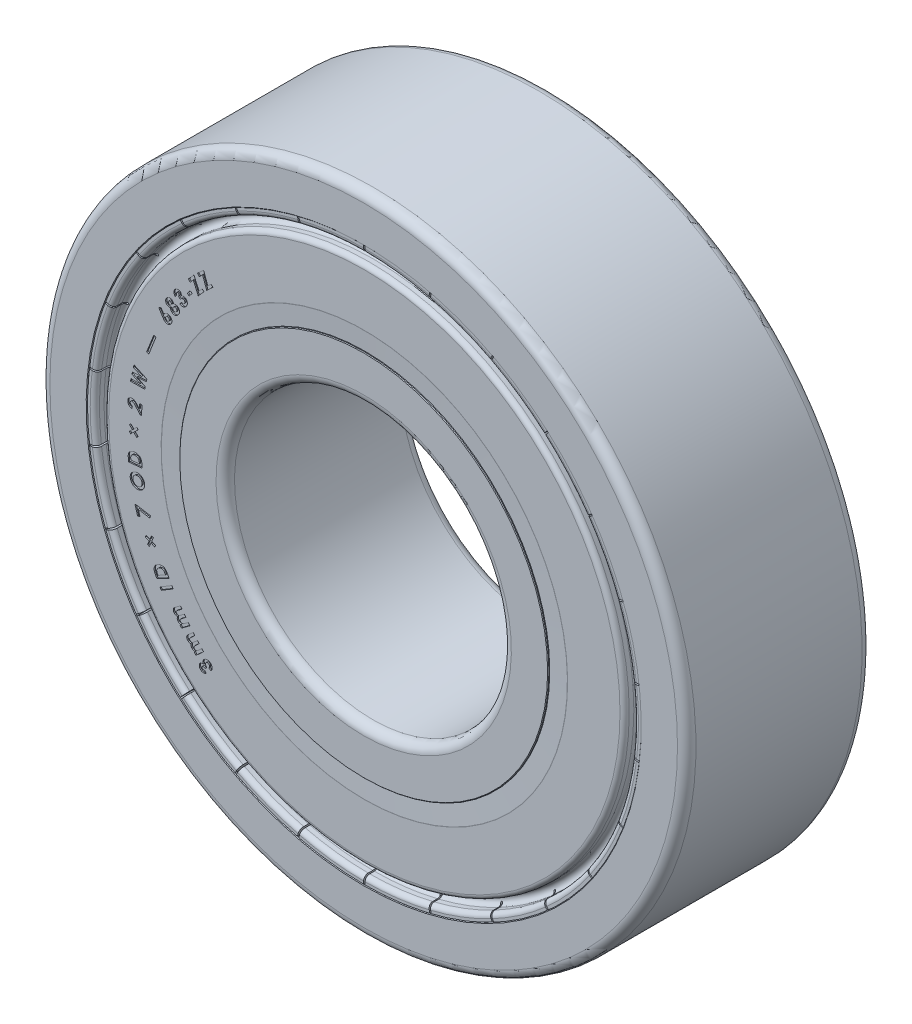
SolidWorks part; units mm, degrees
material "AISI 316 Annealed Stainless Steel Bar (SS)"
ref_plane "Front" through (0, 0, 0) normal (0, 0, 1) x (1, 0, 0)
ref_plane "Top" through (0, 0, 0) normal (0, 1, 0) x (1, 0, 0)
ref_plane "Right" through (0, 0, 0) normal (1, 0, 0) x (0, 0, -1)
sketch "LAYOUT R" plane through (0, 0, 0) normal (1, 0, 0) x (0, 0, -1)
  line L0 (-0.9, 1.5) -> (0.9, 1.5)
  line L1 (1, -3.5) -> (-1, -3.5) construction
  line L2 (1, -3.5) -> (1, 2.5781) construction
  line L3 (0.9, 3.5) -> (-0.9, 3.5)
  line L4 (-1, -3.5) -> (-1, 3.4) construction
  line L6 (2.6982, 0) -> (-2.6982, 0) construction
  line L7 (-0.993, 2) -> (0.993, 2)
  line L8 (-0.993, 3) -> (0.993, 3)
  line L11 (-8.89, 0) -> (8.89, 0) construction
  line L12 (-1, 3.4) -> (-1, 3.007)
  line L13 (1, 3.4) -> (1, 3.007)
  line L16 (-1, 1.993) -> (-1, 1.6)
  line L17 (1, 1.993) -> (1, 1.6)
  line L30 (-0.993, 3) -> (-0.993, 2) construction
  line L31 (0.993, 3) -> (0.993, 2) construction
  line L32 (-0.993, 2.2) -> (0.993, 2.2) construction
  line L33 (-0.993, 2.2) -> (-0.9842, 2)
  line L34 (0.993, 2.2) -> (0.9842, 2)
  line L35 (-0.993, 2.92) -> (0.993, 2.92) construction
  line L38 (-1, 3.007) -> (1, 3.007) construction
  line L39 (-0.993, 3) -> (-0.993, 2.97)
  line L40 (-0.943, 2.92) -> (-0.893, 2.92)
  line L41 (-0.993, 2.2022) -> (-0.993, 2.77)
  line L42 (-0.943, 2.82) -> (-0.893, 2.82)
  line L43 (0.993, 2.2022) -> (0.993, 2.77)
  line L44 (0.943, 2.82) -> (0.893, 2.82)
  line L45 (0.943, 2.92) -> (0.893, 2.92)
  line L46 (-0.993, 2.82) -> (0.993, 2.82) construction
  line L50 (-1.3199, 2.8) -> (1.3199, 2.8) construction
  line L53 (0.993, 2) -> (1, 1.993)
  line L54 (-0.993, 2) -> (-1, 1.993)
  line L56 (-1, 1.993) -> (1, 1.993) construction
  line L57 (1, 3.007) -> (0.993, 3) construction
  line L58 (1, 3.007) -> (0.993, 3)
  line L60 (-1, 3.007) -> (-0.993, 3) construction
  line L61 (-1, 3.007) -> (-0.993, 3)
  line L64 (-0.893, 2.82) -> (-0.893, 2.92) construction
  line L65 (0.893, 2.82) -> (0.893, 2.92) construction
  line L66 (0.993, 3) -> (0.993, 2.97)
  arc A2 (-0.943, 2.82) -> (-0.993, 2.77) centre (-0.943, 2.77) ccw
  arc A3 (0.993, 2.77) -> (0.943, 2.82) centre (0.943, 2.77) ccw
  arc A4 (0.993, 2.2) -> (0.993, 2.2022) centre (0.943, 2.2022) ccw
  arc A5 (-0.993, 2.2022) -> (-0.993, 2.2) centre (-0.943, 2.2022) ccw
  arc A6 (-0.893, 2.82) -> (-0.893, 2.92) centre (-0.893, 2.87) ccw
  arc A7 (0.893, 2.92) -> (0.893, 2.82) centre (0.893, 2.87) ccw
  arc A8 (-0.9, 3.5) -> (-1, 3.4) centre (-0.9, 3.4) ccw
  arc A9 (-1, 1.6) -> (-0.9, 1.5) centre (-0.9, 1.6) ccw
  arc A10 (0.9, 1.5) -> (1, 1.6) centre (0.9, 1.6) ccw
  arc A11 (-0.993, 2.97) -> (-0.943, 2.92) centre (-0.943, 2.97) ccw
  arc A12 (0.943, 2.92) -> (0.993, 2.97) centre (0.943, 2.97) ccw
  arc A13 (1, 3.4) -> (0.9, 3.5) centre (0.9, 3.4) ccw
  point P0 (0, 0)
  point P7 (-0.9, 3.5)
  point P8 (-0.943, 2.92)
  point P15 (0, 0)
  point P29 (-0.993, 2.97)
  point P38 (-0.993, 2.2)
  point P54 (-0.993, 2.77)
  point P55 (-0.943, 2.82)
  point P56 (-0.993, 2.77)
  point P58 (-0.993, 2.2022)
  point P59 (-0.993, 2.2)
  point P60 (0.943, 2.82)
  point P62 (0.993, 2.77)
  point P63 (0.993, 2.2022)
  point P64 (0.993, 2.2)
  point P71 (-1, 3.4)
  point P72 (-1, 1.6)
  point P73 (-0.9, 1.5)
  point P74 (0.9, 1.5)
  point P75 (1, 1.6)
  point P80 (0.9, 3.5)
  point P81 (0.943, 2.92)
  point P88 (0.993, 2.97)
  point P91 (1, 3.4)
  dimension "D21" = 0.1
  dimension "D33" = 0.1
  dimension "D3" = 1.5
  dimension "D4" = 2
  dimension "D5" = 3
  dimension "D24" = 2
  dimension "D6" = 1.993
  dimension "D7" = 1.993
  dimension "D11" = 0.2
  dimension "D12" = 2.5
  dimension "D13" = 2.5
  dimension "D14" = 0.08
  dimension "D17" = 0.007
  dimension "D18" = 0.1
  dimension "D19" = 0.1
  dimension "D20" = 0.1
  dimension "D15" = 0.2
  dimension "D23" = 45
  dimension "D25" = 45
  dimension "D27" = 0.007
  dimension "D28" = 3.5
  dimension "D29" = 2
  dimension "D30" = 7
  dimension "D8" = 1
  dimension "D31" = 45
  dimension "D32" = 45
sketch "Sketch R, INNER BODY" plane through (0, 0, 0) normal (1, 0, 0) x (0, 0, -1)
  line L1 (-0.993, 2) -> (-1, 1.993) construction
  line L3 (-1, 1.993) -> (-1, 1.6) construction
  line L12 (-8.89, 0) -> (8.89, 0) construction
  line L13 (-8.89, 0) -> (8.89, 0) construction
  line L14 (-0.9, 1.5) -> (0.9, 1.5) construction
  line L15 (1, 1.993) -> (1, 1.6) construction
  line L16 (0.993, 2) -> (1, 1.993) construction
  line L17 (-0.993, 2) -> (0.993, 2) construction
  line L18 (-0.993, 2) -> (-1, 1.993)
  line L19 (-1, 1.993) -> (-1, 1.6)
  line L20 (-0.9, 1.5) -> (0.9, 1.5)
  line L21 (1, 1.993) -> (1, 1.6)
  line L22 (0.993, 2) -> (1, 1.993)
  line L23 (-0.993, 2) -> (0.993, 2)
  arc A0 (-1, 1.6) -> (-0.9, 1.5) centre (-0.9, 1.6) ccw construction
  arc A1 (0.9, 1.5) -> (1, 1.6) centre (0.9, 1.6) ccw construction
  arc A2 (-1, 1.6) -> (-0.9, 1.5) centre (-0.9, 1.6) ccw
  arc A3 (0.9, 1.5) -> (1, 1.6) centre (0.9, 1.6) ccw
sketch "Sketch R, OUTER BODY" plane through (0, 0, 0) normal (1, 0, 0) x (0, 0, -1)
  line L8 (-8.89, 0) -> (8.89, 0) construction
  line L9 (-8.89, 0) -> (8.89, 0) construction
  line L31 (-1, 3.4) -> (-1, 3.007) construction
  line L84 (-1, 3.007) -> (-0.993, 3) construction
  line L85 (-0.993, 3) -> (0.993, 3) construction
  line L86 (1, 3.007) -> (0.993, 3) construction
  line L87 (1, 3.4) -> (1, 3.007) construction
  line L88 (0.9, 3.5) -> (-0.9, 3.5) construction
  line L89 (-1, 3.4) -> (-1, 3.007)
  line L90 (-1, 3.007) -> (-0.993, 3)
  line L91 (-0.993, 3) -> (0.993, 3)
  line L92 (1, 3.007) -> (0.993, 3)
  line L93 (1, 3.4) -> (1, 3.007)
  line L94 (0.9, 3.5) -> (-0.9, 3.5)
  arc A6 (1, 3.4) -> (0.9, 3.5) centre (0.9, 3.4) ccw construction
  arc A7 (-0.9, 3.5) -> (-1, 3.4) centre (-0.9, 3.4) ccw construction
  arc A8 (1, 3.4) -> (0.9, 3.5) centre (0.9, 3.4) ccw
  arc A9 (-0.9, 3.5) -> (-1, 3.4) centre (-0.9, 3.4) ccw
sketch "Sketch R, SHIELD FACES" plane through (0, 0, 0) normal (1, 0, 0) x (0, 0, -1)
  line L0 (-8.89, 0) -> (8.89, 0) construction
  line L1 (-8.89, 0) -> (8.89, 0) construction
  line L29 (-0.993, 3) -> (-0.993, 2.97) construction
  line L32 (-0.943, 2.92) -> (-0.893, 2.92) construction
  line L34 (-0.943, 2.82) -> (-0.893, 2.82) construction
  line L36 (-0.993, 2.2022) -> (-0.993, 2.77) construction
  line L38 (-0.993, 2.2) -> (-0.9842, 2) construction
  line L39 (-0.993, 2) -> (0.993, 2) construction
  line L40 (0.993, 2.2) -> (0.9842, 2) construction
  line L43 (0.993, 2.2022) -> (0.993, 2.77) construction
  line L79 (0.943, 2.82) -> (0.893, 2.82) construction
  line L80 (0.943, 2.92) -> (0.893, 2.92) construction
  line L81 (0.993, 3) -> (0.993, 2.97) construction
  line L82 (-0.993, 3) -> (0.993, 3) construction
  line L83 (-0.993, 3) -> (-0.993, 2.97)
  line L84 (-0.943, 2.92) -> (-0.893, 2.92)
  line L85 (-0.943, 2.82) -> (-0.893, 2.82)
  line L86 (-0.993, 2.2022) -> (-0.993, 2.77)
  line L87 (-0.993, 2.2) -> (-0.9842, 2)
  line L88 (-0.9842, 2) -> (0.9842, 2)
  line L89 (0.993, 2.2) -> (0.9842, 2)
  line L90 (0.993, 2.2022) -> (0.993, 2.77)
  line L91 (0.943, 2.82) -> (0.893, 2.82)
  line L92 (0.943, 2.92) -> (0.893, 2.92)
  line L93 (0.993, 3) -> (0.993, 2.97)
  line L94 (-0.993, 3) -> (0.993, 3)
  arc A28 (-0.993, 2.97) -> (-0.943, 2.92) centre (-0.943, 2.97) ccw construction
  arc A29 (-0.893, 2.82) -> (-0.893, 2.92) centre (-0.893, 2.87) ccw construction
  arc A30 (-0.943, 2.82) -> (-0.993, 2.77) centre (-0.943, 2.77) ccw construction
  arc A31 (0.993, 2.77) -> (0.943, 2.82) centre (0.943, 2.77) ccw construction
  arc A32 (0.893, 2.92) -> (0.893, 2.82) centre (0.893, 2.87) ccw construction
  arc A33 (0.943, 2.92) -> (0.993, 2.97) centre (0.943, 2.97) ccw construction
  arc A34 (-0.993, 2.97) -> (-0.943, 2.92) centre (-0.943, 2.97) ccw
  arc A35 (-0.893, 2.82) -> (-0.893, 2.92) centre (-0.893, 2.87) ccw
  arc A36 (-0.943, 2.82) -> (-0.993, 2.77) centre (-0.943, 2.77) ccw
  arc A37 (0.993, 2.77) -> (0.943, 2.82) centre (0.943, 2.77) ccw
  arc A38 (0.893, 2.92) -> (0.893, 2.82) centre (0.893, 2.87) ccw
  arc A39 (0.943, 2.92) -> (0.993, 2.97) centre (0.943, 2.97) ccw
  arc A40 (-0.993, 2.2022) -> (-0.993, 2.2) centre (-0.943, 2.2022) ccw construction
  arc A41 (-0.993, 2.2022) -> (-0.993, 2.2) centre (-0.943, 2.2022) ccw
  arc A42 (0.993, 2.2) -> (0.993, 2.2022) centre (0.943, 2.2022) ccw construction
  arc A43 (0.993, 2.2) -> (0.993, 2.2022) centre (0.943, 2.2022) ccw
revolve "Revolve INNER BODY" add sketch "Sketch R, INNER BODY" angle 360 about L13
revolve "Revolve OUTER BODY" add sketch "Sketch R, OUTER BODY" angle 360 about L9
revolve "Revolve SHIELDS" add sketch "Sketch R, SHIELD FACES" angle 360 about L1
sketch "Sketch TEXT RADIUS 1 — MANUALLY ASSIGN TEXT AND FONT SIZE (FROM EQUATIONS)" plane through (0, 0, 0.993) normal (0, 0, 1) x (1, 0, 0)
  circle A0 centre (0, 0) radius 2.425 construction
  text T0 "<b>3mm ID × 7 OD × 2 W  —  683-ZZ</b>" font "Century Gothic" height 0.15
  dimension "D1" = 4.85
extrude "Cut-Extrude LABEL 1" cut sketch "Sketch TEXT RADIUS 1 — MANUALLY ASSIGN TEXT AND FONT SIZE (FROM EQUATIONS)" against normal blind 0.0127
sketch "Sketch TEXT RADIUS 2 — MANUALLY ASSIGN TEXT AND FONT SIZE (FROM EQUATIONS)" plane through (0, 0, -0.993) normal (0, 0, -1) x (-1, 0, 0)
  circle A0 centre (0, 0) radius 2.425 construction
  text T0 "<b>3mm ID × 7 OD × 2 W  —  683-ZZ</b>" font "Century Gothic" height 0.15
  dimension "D1" = 4.85
extrude "Cut-Extrude LABEL 2" cut sketch "Sketch TEXT RADIUS 2 — MANUALLY ASSIGN TEXT AND FONT SIZE (FROM EQUATIONS)" against normal blind 0.0127
sketch "LAYOUT F, SLIT SEED" plane through (0, 0, 0) normal (0, 0, 1) x (1, 0, 0)
  line L0 (0, 0) -> (0, 12.7) construction
  line L3 (0.008, 3) -> (0.008, 2.9089)
  line L4 (-0.008, 3) -> (-0.008, 2.9089)
  circle A4 centre (0, 0) radius 2.9
  circle A5 centre (0, 0) radius 3
  circle A6 centre (0, 2.9) radius 0.012
  point P13 (-0.008, 3)
  point P15 (0.008, 3)
  dimension "D1" = 6
  dimension "D2" = 5.8
  dimension "D3" = 0.024
  dimension "D4" = 0.008
  dimension "D5" = 0.008
sketch "Sketch F, SLIT SEED" plane through (0, 0, 0.993) normal (0, 0, 1) x (1, 0, 0)
  line L1 (0.008, 3) -> (0.008, 2.9089) construction
  line L8 (-0.008, 3) -> (-0.008, 2.9089) construction
  line L9 (0.008, 3) -> (0.008, 2.9089)
  line L10 (-0.008, 3) -> (-0.008, 2.9089)
  circle A1 centre (0, 2.9) radius 0.012 construction
  circle A8 centre (0, 0) radius 3 construction
  arc A9 (-0.008, 2.9089) -> (0.008, 2.9089) centre (0, 2.9) ccw
  arc A10 (0.008, 3) -> (-0.008, 3) centre (0, 0) ccw
extrude "Cut-Extrude SLIT SEED F" cut sketch "Sketch F, SLIT SEED" along normal blind 0.635 from surface starting at face at (2.0812, 1.388, -0.993)
extrude "Cut-Extrude SLIT SEED B" cut sketch "Sketch F, SLIT SEED<2>" against normal blind 0.635
sketch "Sketch F, SLIT SEED<2>" plane through (0, 0, 0.993) normal (0, 0, 1) x (1, 0, 0) same geometry as "Sketch F, SLIT SEED"
pattern_circular "CirPattern1" count 26 over 360 of "Cut-Extrude SLIT SEED F"
pattern_circular "CirPattern2" count 26 over 360 of "Cut-Extrude SLIT SEED B" reverse direction yes
equation "\"_i__BORE\" = 3"
equation "\"_i__OUTSIDE_DIAMETER\" = 7"
equation "\"_i__WIDTH\"= 2"
equation "\"_user_applied_FONT_SIZE\"= int ( \"BODY_SPAN__SHIELD__OF_RADIUS\" * \"g_param__FONT_SIZE_RATIO\" * 100 ) / 100'MANUALLY ASSIGN TO FONT"
equation "\"BODY__HALF_WIDTH\"= \"_i__WIDTH\" / 2"
equation "\"BODY_SPAN___OF_DIAMETER\"= \"_i__OUTSIDE_DIAMETER\" - \"_i__BORE\""
equation "\"BODY_SPAN___OF_RADIUS\"= \"BODY_SPAN___OF_DIAMETER\" / 2"
equation "\"BODY_SPAN__BORE_AND_OD__OF RADIUS\"= ( \"BODY_SPAN___OF_RADIUS\" - \"BODY_SPAN__SHIELD__OF_RADIUS\" ) / 2"
equation "\"BODY_SPAN__SHIELD__OF_RADIUS\"= \"BODY_SPAN___OF_RADIUS\" * \"g_param__SHIELD_PANEL_SPAN__RATIO_OF_BODY_RADIAN\""
equation "\"BORE__RADIUS\"= \"_i__BORE\" / 2"
equation "\"CORNER_RADII\"= \"_i__WIDTH\" * \"g_param__CORNER_RADII__RATIO_TO_WIDTH\""
equation "\"OUTSIDE_RADIUS\"= \"_i__OUTSIDE_DIAMETER\" / 2"
equation "\"RING_INNER__OUTSIDE_RADIUS\"= \"BORE__RADIUS\" + \"BODY_SPAN__BORE_AND_OD__OF RADIUS\""
equation "\"RING_OUTER__INSIDE_DIAMETER\"= \"RING_OUTER__INSIDE_RADIUS\" * 2"
equation "\"RING_OUTER__INSIDE_RADIUS\"= ( \"_i__OUTSIDE_DIAMETER\" / 2 ) - \"BODY_SPAN__BORE_AND_OD__OF RADIUS\""
equation "\"SHIELD__BOTTOM_AND_TOP_REGIONS_SPAN\"= \"BODY_SPAN__SHIELD__OF_RADIUS\" * \"g_param__SHIELD__TOP_AND_BOTTOM_REGIONS_RATIO\""
equation "\"SHIELD__COMPRESSION_FILLET_DIAMETER\"= \"BODY_SPAN__SHIELD__OF_RADIUS\" * \"g_param__SHIELD_COMPRESSION_FILLET_DIAMETER_RATIO\""
equation "\"SHIELD__COMPRESSION_FILLET_RADIUS\"= \"SHIELD__COMPRESSION_FILLET_DIAMETER\" / 2"
equation "\"SHIELD__FACE_FILLET_DIAMETER\"= \"BODY_SPAN__SHIELD__OF_RADIUS\" * \"g_param__SHIELD_FACE_FILLET_RATIO\""
equation "\"SHIELD__FACE_INSET\"= \"SIDE_FACE_CHAMFERS\""
equation "\"SHIELD__FACE_TO_OPPOSING_BRG_BODY_FACE\"= \"_i__WIDTH\" - \"SHIELD__FACE_INSET\""
equation "\"SHIELD__HALF_SLIT_WIDTH\"= \"SHIELD__SLIT_WIDTH\" / 2"
equation "\"SHIELD__HALF_WALL\"= \"SHIELD__WALL\" / 2"
equation "\"SHIELD__SLIT_WIDTH\"= \"SHIELD__WALL\" / 5"
equation "\"SHIELD__WALL\"= \"BODY_SPAN__SHIELD__OF_RADIUS\" * \"g_param__SHIELD_WALL_TO_SPAN_RATIO\""
equation "\"SHIELD_SLIT__INSIDE_TERMINUS__DIAMETER\"= \"RING_OUTER__INSIDE_DIAMETER\" - \"SHIELD__BOTTOM_AND_TOP_REGIONS_SPAN\""
equation "\"SHIELD_SLIT__KEYHOLE_DIAMETER\"= \"SHIELD__SLIT_WIDTH\" * 1.5"
equation "\"SIDE_FACE_CHAMFERS\"= \"_i__OUTSIDE_DIAMETER\" * \"g_param__SIDE_CHAMFERS__RATIO_TO_OD\""
equation "\"TEXT_RADIUS\"= \"_i__BORE\" + ( \"BODY_SPAN___OF_DIAMETER\" / 2 ) - \"_user_applied_FONT_SIZE\""
equation "\"WIDTH__HALF\"= \"_i__WIDTH\" / 2"
equation "\"D1@CirPattern1\" = \"g_param__SHIELD__NUMBER_OF_SLITS\""
equation "\"D1@CirPattern2\" = \"g_param__SHIELD__NUMBER_OF_SLITS\""
equation "\"D1@LAYOUT F, SLIT SEED\"=\"RING_OUTER__INSIDE_DIAMETER\""
equation "\"D1@Sketch TEXT RADIUS 1 — MANUALLY ASSIGN TEXT AND FONT SIZE (FROM EQUATIONS)\" = \"TEXT_RADIUS\""
equation "\"D1@Sketch TEXT RADIUS 2 — MANUALLY ASSIGN TEXT AND FONT SIZE (FROM EQUATIONS)\" = \"TEXT_RADIUS\""
equation "\"D11@LAYOUT R\"=\"SHIELD__BOTTOM_AND_TOP_REGIONS_SPAN\""
equation "\"D12@LAYOUT R\" = \"g_param__SHIELD__INSIDE_BEVEL_ANGLE__DEGREES\""
equation "\"D13@LAYOUT R\"= \"g_param__SHIELD__INSIDE_BEVEL_ANGLE__DEGREES\""
equation "\"D14@LAYOUT R\"=\"SHIELD__WALL\""
equation "\"D15@LAYOUT R\"=\"SHIELD__BOTTOM_AND_TOP_REGIONS_SPAN\""
equation "\"D17@LAYOUT R\"=\"SIDE_FACE_CHAMFERS\""
equation "\"D18@LAYOUT R\"=\"SHIELD__COMPRESSION_FILLET_DIAMETER\""
equation "\"D19@LAYOUT R\"=\"SHIELD__COMPRESSION_FILLET_DIAMETER\""
equation "\"D2@LAYOUT F, SLIT SEED\"=\"SHIELD_SLIT__INSIDE_TERMINUS__DIAMETER\""
equation "\"D20@LAYOUT R\"=\"SHIELD__COMPRESSION_FILLET_DIAMETER\""
equation "\"D21@LAYOUT R\"=\"SHIELD__FACE_FILLET_DIAMETER\""
equation "\"D24@LAYOUT R\"=\"_i__WIDTH\""
equation "\"D27@LAYOUT R\"=\"SIDE_FACE_CHAMFERS\""
equation "\"D28@LAYOUT R\"=\"OUTSIDE_RADIUS\""
equation "\"D3@LAYOUT F, SLIT SEED\"=\"SHIELD_SLIT__KEYHOLE_DIAMETER\""
equation "\"D3@LAYOUT R\"=\"BORE__RADIUS\""
equation "\"D30@LAYOUT R\"=\"_i__OUTSIDE_DIAMETER\""
equation "\"D33@LAYOUT R\"=\"CORNER_RADII\""
equation "\"D4@LAYOUT F, SLIT SEED\"=\"SHIELD__HALF_SLIT_WIDTH\""
equation "\"D4@LAYOUT R\"=\"RING_INNER__OUTSIDE_RADIUS\""
equation "\"D5@LAYOUT F, SLIT SEED\"=\"SHIELD__HALF_SLIT_WIDTH\""
equation "\"D5@LAYOUT R\"=\"RING_OUTER__INSIDE_RADIUS\""
equation "\"D6@LAYOUT R\"=\"SHIELD__FACE_TO_OPPOSING_BRG_BODY_FACE\""
equation "\"D7@LAYOUT R\"=\"SHIELD__FACE_TO_OPPOSING_BRG_BODY_FACE\""
equation "\"D8@LAYOUT R\"=\"WIDTH__HALF\""
equation "\"g_param__CORNER_RADII__RATIO_TO_WIDTH\"= 0.05'ISO MAX IS 0.07 WHERE WIDTH IS LESS THAN DIAMETER"
equation "\"g_param__FONT_SIZE_RATIO\"= 0.15'EXPRESSES RADIAL PROPORTION OF SHIELD FACE"
equation "\"g_param__INDICIA__EXTRUSION_DEPTH\"=0.013'CONCAVE-EMBOSSED INDICIA ON SHIELD FACES"
equation "\"g_param__SHIELD__INSIDE_BEVEL_ANGLE__DEGREES\"= 2.5'SHOULD BE GREATER THAN 0 AND LESS THAN OR EQUAL TO 10, ORIGINALLY 1"
equation "\"g_param__SHIELD__NUMBER_OF_SLITS\"=26'OPTIONAL NUMBER OF SHIELD COMPRESSION RING SLITS"
equation "\"g_param__SHIELD__TOP_AND_BOTTOM_REGIONS_RATIO\"=0.2'PART OF RADIAL SHIELD SPAN OCCUPIED BY INMOST BEVEL, ORIGINALLY 0.2"
equation "\"g_param__SHIELD_COMPRESSION_FILLET_DIAMETER_RATIO\"=0.1'ORIGINALLY 0,1"
equation "\"g_param__SHIELD_FACE_FILLET_RATIO\"=0.1'ORIGINALLY 0.1"
equation "\"g_param__SHIELD_FACE_INSET__RATIO_OF_WIDTH\"= 0.035'ISO-UNSPECIFIED, SHOULD BE AT LEAST 0.025 and LESS THAN 0.036"
equation "\"g_param__SHIELD_PANEL_SPAN__RATIO_OF_BODY_RADIAN\"= 0.5'ISO-UNSPECIFIED, ORIGINALLY 0.5"
equation "\"g_param__SHIELD_WALL_TO_SPAN_RATIO\"=0.08'SHOULD BE LESS THAN 0.015, ORIGINALLY 0.08, PRESCRIBES MATERIAL THICKNESS"
equation "\"g_param__SIDE_CHAMFERS__RATIO_TO_OD\"= 0.001'NOT ISO-SPECIFIED"
